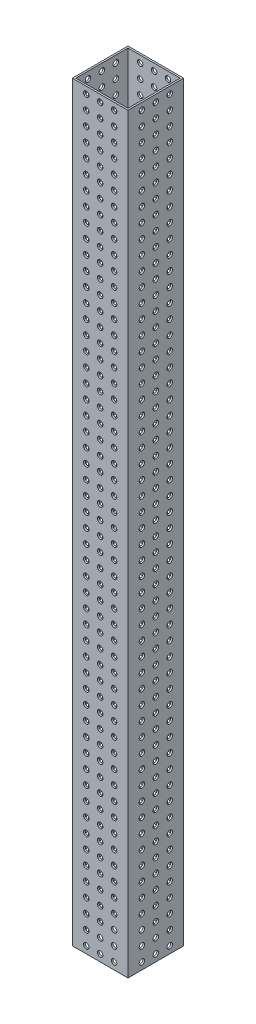
SolidWorks part; units mm, degrees
ref_plane "Front Plane" through (0, 0, 0) normal (0, 0, 1) x (1, 0, 0)
ref_plane "Top Plane" through (0, 0, 0) normal (0, 1, 0) x (1, 0, 0)
ref_plane "Right Plane" through (0, 0, 0) normal (1, 0, 0) x (0, 0, -1)
sketch "Sketch1" plane through (0, 0, 0) normal (0, 1, 0) x (1, 0, 0)
  line L1 (-25.4, 25.4) -> (25.4, 25.4)
  line L2 (-25.4, 25.4) -> (-25.4, -25.4)
  line L3 (-25.4, -25.4) -> (25.4, -25.4)
  line L4 (25.4, 25.4) -> (25.4, -25.4)
  line L5 (-25.4, 25.4) -> (25.4, -25.4) construction
  line L6 (-25.4, -25.4) -> (25.4, 25.4) construction
  line L7 (23.8125, 23.8125) -> (-23.8125, 23.8125)
  line L8 (23.8125, 23.8125) -> (23.8125, -23.8125)
  line L9 (23.8125, -23.8125) -> (-23.8125, -23.8125)
  line L10 (-23.8125, 23.8125) -> (-23.8125, -23.8125)
  line L11 (23.8125, 23.8125) -> (-23.8125, -23.8125) construction
  line L12 (23.8125, -23.8125) -> (-23.8125, 23.8125) construction
  point P0 (0, 0)
  point P6 (0, 0)
  dimension "D1" = 50.8
  dimension "D2" = 50.8
  dimension "D3" = 1.5875
  dimension "D4" = 1.5875
extrude "Boss-Extrude1" add sketch "Sketch1" along normal blind 685.8
sketch "Sketch2" plane through (0, 0, 25.4) normal (0, 0, 1) x (1, 0, 0)
  line L0 (0, 685.8) -> (0, 0) construction
  line L1 (-25.4, 685.8) -> (25.4, 685.8) construction
  line L2 (-25.4, 685.8) -> (-25.4, 0) construction
  line L3 (-6.35, -314.2) -> (-6.35, 49685.8) construction
  circle A0 centre (-12.7, 679.45) radius 2.4892
  circle A1 centre (-12.7, 666.75) radius 2.4892
  circle A2 centre (-12.7, 654.05) radius 2.4892
  circle A3 centre (-12.7, 641.35) radius 2.4892
  circle A4 centre (-12.7, 628.65) radius 2.4892
  circle A5 centre (-12.7, 615.95) radius 2.4892
  circle A6 centre (-12.7, 603.25) radius 2.4892
  circle A7 centre (-12.7, 590.55) radius 2.4892
  circle A8 centre (-12.7, 577.85) radius 2.4892
  circle A9 centre (-12.7, 565.15) radius 2.4892
  circle A10 centre (-12.7, 552.45) radius 2.4892
  circle A11 centre (-12.7, 539.75) radius 2.4892
  circle A12 centre (-12.7, 527.05) radius 2.4892
  circle A13 centre (-12.7, 514.35) radius 2.4892
  circle A14 centre (-12.7, 501.65) radius 2.4892
  circle A15 centre (-12.7, 488.95) radius 2.4892
  circle A16 centre (-12.7, 476.25) radius 2.4892
  circle A17 centre (-12.7, 463.55) radius 2.4892
  circle A18 centre (-12.7, 450.85) radius 2.4892
  circle A19 centre (-12.7, 438.15) radius 2.4892
  circle A20 centre (-12.7, 425.45) radius 2.4892
  circle A21 centre (-12.7, 412.75) radius 2.4892
  circle A22 centre (-12.7, 400.05) radius 2.4892
  circle A23 centre (-12.7, 387.35) radius 2.4892
  circle A24 centre (-12.7, 374.65) radius 2.4892
  circle A25 centre (-12.7, 361.95) radius 2.4892
  circle A26 centre (-12.7, 349.25) radius 2.4892
  circle A27 centre (-12.7, 336.55) radius 2.4892
  circle A28 centre (-12.7, 323.85) radius 2.4892
  circle A29 centre (-12.7, 311.15) radius 2.4892
  circle A30 centre (-12.7, 298.45) radius 2.4892
  circle A31 centre (-12.7, 285.75) radius 2.4892
  circle A32 centre (-12.7, 273.05) radius 2.4892
  circle A33 centre (-12.7, 260.35) radius 2.4892
  circle A34 centre (-12.7, 247.65) radius 2.4892
  circle A35 centre (-12.7, 234.95) radius 2.4892
  circle A36 centre (-12.7, 222.25) radius 2.4892
  circle A37 centre (-12.7, 209.55) radius 2.4892
  circle A38 centre (-12.7, 196.85) radius 2.4892
  circle A39 centre (-12.7, 184.15) radius 2.4892
  circle A40 centre (-12.7, 171.45) radius 2.4892
  circle A41 centre (-12.7, 158.75) radius 2.4892
  circle A42 centre (-12.7, 146.05) radius 2.4892
  circle A43 centre (-12.7, 133.35) radius 2.4892
  circle A44 centre (-12.7, 120.65) radius 2.4892
  circle A45 centre (-12.7, 107.95) radius 2.4892
  circle A46 centre (-12.7, 95.25) radius 2.4892
  circle A47 centre (-12.7, 82.55) radius 2.4892
  circle A48 centre (-12.7, 69.85) radius 2.4892
  circle A49 centre (-12.7, 57.15) radius 2.4892
  circle A50 centre (-12.7, 44.45) radius 2.4892
  circle A51 centre (-12.7, 31.75) radius 2.4892
  circle A52 centre (-12.7, 19.05) radius 2.4892
  circle A53 centre (-12.7, 6.35) radius 2.4892
  circle A54 centre (12.7, 6.35) radius 2.4892
  circle A55 centre (12.7, 19.05) radius 2.4892
  circle A56 centre (12.7, 31.75) radius 2.4892
  circle A57 centre (12.7, 44.45) radius 2.4892
  circle A58 centre (12.7, 57.15) radius 2.4892
  circle A59 centre (12.7, 69.85) radius 2.4892
  circle A60 centre (12.7, 82.55) radius 2.4892
  circle A61 centre (12.7, 95.25) radius 2.4892
  circle A62 centre (12.7, 107.95) radius 2.4892
  circle A63 centre (12.7, 120.65) radius 2.4892
  circle A64 centre (12.7, 133.35) radius 2.4892
  circle A65 centre (12.7, 146.05) radius 2.4892
  circle A66 centre (12.7, 158.75) radius 2.4892
  circle A67 centre (12.7, 171.45) radius 2.4892
  circle A68 centre (12.7, 184.15) radius 2.4892
  circle A69 centre (12.7, 196.85) radius 2.4892
  circle A70 centre (12.7, 209.55) radius 2.4892
  circle A71 centre (12.7, 222.25) radius 2.4892
  circle A72 centre (12.7, 234.95) radius 2.4892
  circle A73 centre (12.7, 247.65) radius 2.4892
  circle A74 centre (12.7, 260.35) radius 2.4892
  circle A75 centre (12.7, 273.05) radius 2.4892
  circle A76 centre (12.7, 285.75) radius 2.4892
  circle A77 centre (12.7, 298.45) radius 2.4892
  circle A78 centre (12.7, 311.15) radius 2.4892
  circle A79 centre (12.7, 323.85) radius 2.4892
  circle A80 centre (12.7, 336.55) radius 2.4892
  circle A81 centre (12.7, 374.65) radius 2.4892
  circle A82 centre (12.7, 361.95) radius 2.4892
  circle A83 centre (12.7, 349.25) radius 2.4892
  circle A84 centre (12.7, 387.35) radius 2.4892
  circle A85 centre (12.7, 400.05) radius 2.4892
  circle A86 centre (12.7, 412.75) radius 2.4892
  circle A87 centre (12.7, 425.45) radius 2.4892
  circle A88 centre (12.7, 438.15) radius 2.4892
  circle A89 centre (12.7, 450.85) radius 2.4892
  circle A90 centre (12.7, 463.55) radius 2.4892
  circle A91 centre (12.7, 476.25) radius 2.4892
  circle A92 centre (12.7, 488.95) radius 2.4892
  circle A93 centre (12.7, 501.65) radius 2.4892
  circle A94 centre (12.7, 514.35) radius 2.4892
  circle A95 centre (12.7, 527.05) radius 2.4892
  circle A96 centre (12.7, 539.75) radius 2.4892
  circle A97 centre (12.7, 552.45) radius 2.4892
  circle A98 centre (12.7, 565.15) radius 2.4892
  circle A99 centre (12.7, 577.85) radius 2.4892
  circle A100 centre (12.7, 590.55) radius 2.4892
  circle A101 centre (12.7, 603.25) radius 2.4892
  circle A102 centre (12.7, 615.95) radius 2.4892
  circle A103 centre (12.7, 628.65) radius 2.4892
  circle A104 centre (12.7, 641.35) radius 2.4892
  circle A105 centre (12.7, 654.05) radius 2.4892
  circle A106 centre (12.7, 666.75) radius 2.4892
  circle A107 centre (12.7, 679.45) radius 2.4892
  circle A108 centre (0, 6.35) radius 2.4892
  circle A109 centre (0, 19.05) radius 2.4892
  circle A110 centre (0, 31.75) radius 2.4892
  circle A111 centre (0, 44.45) radius 2.4892
  circle A112 centre (0, 57.15) radius 2.4892
  circle A113 centre (0, 69.85) radius 2.4892
  circle A114 centre (0, 82.55) radius 2.4892
  circle A115 centre (0, 95.25) radius 2.4892
  circle A116 centre (0, 107.95) radius 2.4892
  circle A117 centre (0, 120.65) radius 2.4892
  circle A118 centre (0, 133.35) radius 2.4892
  circle A119 centre (0, 146.05) radius 2.4892
  circle A120 centre (0, 158.75) radius 2.4892
  circle A121 centre (0, 171.45) radius 2.4892
  circle A122 centre (0, 184.15) radius 2.4892
  circle A123 centre (0, 196.85) radius 2.4892
  circle A124 centre (0, 209.55) radius 2.4892
  circle A125 centre (0, 222.25) radius 2.4892
  circle A126 centre (0, 234.95) radius 2.4892
  circle A127 centre (0, 247.65) radius 2.4892
  circle A128 centre (0, 260.35) radius 2.4892
  circle A129 centre (0, 273.05) radius 2.4892
  circle A130 centre (0, 285.75) radius 2.4892
  circle A131 centre (0, 298.45) radius 2.4892
  circle A132 centre (0, 311.15) radius 2.4892
  circle A133 centre (0, 323.85) radius 2.4892
  circle A134 centre (0, 336.55) radius 2.4892
  circle A135 centre (0, 349.25) radius 2.4892
  circle A136 centre (0, 361.95) radius 2.4892
  circle A137 centre (0, 374.65) radius 2.4892
  circle A138 centre (0, 387.35) radius 2.4892
  circle A139 centre (0, 400.05) radius 2.4892
  circle A140 centre (0, 412.75) radius 2.4892
  circle A141 centre (0, 425.45) radius 2.4892
  circle A142 centre (0, 438.15) radius 2.4892
  circle A143 centre (0, 450.85) radius 2.4892
  circle A144 centre (0, 463.55) radius 2.4892
  circle A145 centre (0, 476.25) radius 2.4892
  circle A146 centre (0, 488.95) radius 2.4892
  circle A147 centre (0, 501.65) radius 2.4892
  circle A148 centre (0, 514.35) radius 2.4892
  circle A149 centre (0, 527.05) radius 2.4892
  circle A150 centre (0, 539.75) radius 2.4892
  circle A151 centre (0, 552.45) radius 2.4892
  circle A152 centre (0, 565.15) radius 2.4892
  circle A153 centre (0, 577.85) radius 2.4892
  circle A154 centre (0, 590.55) radius 2.4892
  circle A155 centre (0, 603.25) radius 2.4892
  circle A156 centre (0, 615.95) radius 2.4892
  circle A157 centre (0, 628.65) radius 2.4892
  circle A158 centre (0, 641.35) radius 2.4892
  circle A159 centre (0, 654.05) radius 2.4892
  circle A160 centre (0, 666.75) radius 2.4892
  circle A161 centre (0, 679.45) radius 2.4892
  dimension "D1" = 4.9784
  dimension "D2" = 6.35
  dimension "D3" = 12.7
  dimension "D5" = 12.7
  dimension "D6" = 6.35
  dimension "D4" = 54
extrude "Cut-Extrude1" cut sketch "Sketch2" against normal through all
sketch "Sketch4" plane through (25.4, 0, 0) normal (1, 0, 0) x (0, 0, -1)
  line L0 (0, 685.8) -> (0, 0) construction
  line L1 (-25.4, 685.8) -> (25.4, 685.8) construction
  line L2 (-25.4, 685.8) -> (-25.4, 0) construction
  line L3 (-6.35, -314.2) -> (-6.35, 49685.8) construction
  circle A0 centre (-12.7, 679.45) radius 2.4892
  circle A1 centre (-12.7, 666.75) radius 2.4892
  circle A2 centre (-12.7, 654.05) radius 2.4892
  circle A3 centre (-12.7, 641.35) radius 2.4892
  circle A4 centre (-12.7, 628.65) radius 2.4892
  circle A5 centre (-12.7, 615.95) radius 2.4892
  circle A6 centre (-12.7, 603.25) radius 2.4892
  circle A7 centre (-12.7, 590.55) radius 2.4892
  circle A8 centre (-12.7, 577.85) radius 2.4892
  circle A9 centre (-12.7, 565.15) radius 2.4892
  circle A10 centre (-12.7, 552.45) radius 2.4892
  circle A11 centre (-12.7, 539.75) radius 2.4892
  circle A12 centre (-12.7, 527.05) radius 2.4892
  circle A13 centre (-12.7, 514.35) radius 2.4892
  circle A14 centre (-12.7, 501.65) radius 2.4892
  circle A15 centre (-12.7, 488.95) radius 2.4892
  circle A16 centre (-12.7, 476.25) radius 2.4892
  circle A17 centre (-12.7, 463.55) radius 2.4892
  circle A18 centre (-12.7, 450.85) radius 2.4892
  circle A19 centre (-12.7, 438.15) radius 2.4892
  circle A20 centre (-12.7, 425.45) radius 2.4892
  circle A21 centre (-12.7, 412.75) radius 2.4892
  circle A22 centre (-12.7, 400.05) radius 2.4892
  circle A23 centre (-12.7, 387.35) radius 2.4892
  circle A24 centre (-12.7, 374.65) radius 2.4892
  circle A25 centre (-12.7, 361.95) radius 2.4892
  circle A26 centre (-12.7, 349.25) radius 2.4892
  circle A27 centre (-12.7, 336.55) radius 2.4892
  circle A28 centre (-12.7, 323.85) radius 2.4892
  circle A29 centre (-12.7, 311.15) radius 2.4892
  circle A30 centre (-12.7, 298.45) radius 2.4892
  circle A31 centre (-12.7, 285.75) radius 2.4892
  circle A32 centre (-12.7, 273.05) radius 2.4892
  circle A33 centre (-12.7, 260.35) radius 2.4892
  circle A34 centre (-12.7, 247.65) radius 2.4892
  circle A35 centre (-12.7, 234.95) radius 2.4892
  circle A36 centre (-12.7, 222.25) radius 2.4892
  circle A37 centre (-12.7, 209.55) radius 2.4892
  circle A38 centre (-12.7, 196.85) radius 2.4892
  circle A39 centre (-12.7, 184.15) radius 2.4892
  circle A40 centre (-12.7, 171.45) radius 2.4892
  circle A41 centre (-12.7, 158.75) radius 2.4892
  circle A42 centre (-12.7, 146.05) radius 2.4892
  circle A43 centre (-12.7, 133.35) radius 2.4892
  circle A44 centre (-12.7, 120.65) radius 2.4892
  circle A45 centre (-12.7, 107.95) radius 2.4892
  circle A46 centre (-12.7, 95.25) radius 2.4892
  circle A47 centre (-12.7, 82.55) radius 2.4892
  circle A48 centre (-12.7, 69.85) radius 2.4892
  circle A49 centre (-12.7, 57.15) radius 2.4892
  circle A50 centre (-12.7, 44.45) radius 2.4892
  circle A51 centre (-12.7, 31.75) radius 2.4892
  circle A52 centre (-12.7, 19.05) radius 2.4892
  circle A53 centre (-12.7, 6.35) radius 2.4892
  circle A54 centre (12.7, 273.05) radius 2.4892
  circle A55 centre (12.7, 285.75) radius 2.4892
  circle A56 centre (12.7, 298.45) radius 2.4892
  circle A57 centre (12.7, 311.15) radius 2.4892
  circle A58 centre (12.7, 323.85) radius 2.4892
  circle A59 centre (12.7, 336.55) radius 2.4892
  circle A60 centre (12.7, 349.25) radius 2.4892
  circle A61 centre (12.7, 361.95) radius 2.4892
  circle A62 centre (12.7, 374.65) radius 2.4892
  circle A63 centre (12.7, 387.35) radius 2.4892
  circle A64 centre (12.7, 400.05) radius 2.4892
  circle A65 centre (12.7, 412.75) radius 2.4892
  circle A66 centre (12.7, 425.45) radius 2.4892
  circle A67 centre (12.7, 438.15) radius 2.4892
  circle A68 centre (12.7, 450.85) radius 2.4892
  circle A69 centre (12.7, 463.55) radius 2.4892
  circle A70 centre (12.7, 476.25) radius 2.4892
  circle A71 centre (12.7, 488.95) radius 2.4892
  circle A72 centre (12.7, 501.65) radius 2.4892
  circle A73 centre (12.7, 514.35) radius 2.4892
  circle A74 centre (12.7, 527.05) radius 2.4892
  circle A75 centre (12.7, 539.75) radius 2.4892
  circle A76 centre (12.7, 552.45) radius 2.4892
  circle A77 centre (12.7, 565.15) radius 2.4892
  circle A78 centre (12.7, 577.85) radius 2.4892
  circle A79 centre (12.7, 590.55) radius 2.4892
  circle A80 centre (12.7, 603.25) radius 2.4892
  circle A81 centre (12.7, 615.95) radius 2.4892
  circle A82 centre (12.7, 628.65) radius 2.4892
  circle A83 centre (12.7, 641.35) radius 2.4892
  circle A84 centre (12.7, 654.05) radius 2.4892
  circle A85 centre (12.7, 666.75) radius 2.4892
  circle A86 centre (12.7, 19.05) radius 2.4892
  circle A87 centre (12.7, 31.75) radius 2.4892
  circle A88 centre (12.7, 44.45) radius 2.4892
  circle A89 centre (12.7, 57.15) radius 2.4892
  circle A90 centre (12.7, 69.85) radius 2.4892
  circle A91 centre (12.7, 82.55) radius 2.4892
  circle A92 centre (12.7, 95.25) radius 2.4892
  circle A93 centre (12.7, 107.95) radius 2.4892
  circle A94 centre (12.7, 120.65) radius 2.4892
  circle A95 centre (12.7, 133.35) radius 2.4892
  circle A96 centre (12.7, 146.05) radius 2.4892
  circle A97 centre (12.7, 158.75) radius 2.4892
  circle A98 centre (12.7, 171.45) radius 2.4892
  circle A99 centre (12.7, 184.15) radius 2.4892
  circle A100 centre (12.7, 196.85) radius 2.4892
  circle A101 centre (12.7, 209.55) radius 2.4892
  circle A102 centre (12.7, 222.25) radius 2.4892
  circle A103 centre (12.7, 234.95) radius 2.4892
  circle A104 centre (12.7, 247.65) radius 2.4892
  circle A105 centre (12.7, 260.35) radius 2.4892
  circle A106 centre (12.7, 6.35) radius 2.4892
  circle A107 centre (12.7, 679.45) radius 2.4892
  circle A108 centre (0, 82.55) radius 2.4892
  circle A109 centre (0, 19.05) radius 2.4892
  circle A110 centre (0, 31.75) radius 2.4892
  circle A111 centre (0, 44.45) radius 2.4892
  circle A112 centre (0, 57.15) radius 2.4892
  circle A113 centre (0, 69.85) radius 2.4892
  circle A114 centre (0, 95.25) radius 2.4892
  circle A115 centre (0, 107.95) radius 2.4892
  circle A116 centre (0, 120.65) radius 2.4892
  circle A117 centre (0, 133.35) radius 2.4892
  circle A118 centre (0, 146.05) radius 2.4892
  circle A119 centre (0, 158.75) radius 2.4892
  circle A120 centre (0, 171.45) radius 2.4892
  circle A121 centre (0, 184.15) radius 2.4892
  circle A122 centre (0, 196.85) radius 2.4892
  circle A123 centre (0, 209.55) radius 2.4892
  circle A124 centre (0, 222.25) radius 2.4892
  circle A125 centre (0, 234.95) radius 2.4892
  circle A126 centre (0, 247.65) radius 2.4892
  circle A127 centre (0, 260.35) radius 2.4892
  circle A128 centre (0, 273.05) radius 2.4892
  circle A129 centre (0, 285.75) radius 2.4892
  circle A130 centre (0, 298.45) radius 2.4892
  circle A131 centre (0, 311.15) radius 2.4892
  circle A132 centre (0, 323.85) radius 2.4892
  circle A133 centre (0, 336.55) radius 2.4892
  circle A134 centre (0, 361.95) radius 2.4892
  circle A135 centre (0, 374.65) radius 2.4892
  circle A136 centre (0, 387.35) radius 2.4892
  circle A137 centre (0, 400.05) radius 2.4892
  circle A138 centre (0, 412.75) radius 2.4892
  circle A139 centre (0, 425.45) radius 2.4892
  circle A140 centre (0, 438.15) radius 2.4892
  circle A141 centre (0, 450.85) radius 2.4892
  circle A142 centre (0, 463.55) radius 2.4892
  circle A143 centre (0, 476.25) radius 2.4892
  circle A144 centre (0, 488.95) radius 2.4892
  circle A145 centre (0, 501.65) radius 2.4892
  circle A146 centre (0, 514.35) radius 2.4892
  circle A147 centre (0, 527.05) radius 2.4892
  circle A148 centre (0, 539.75) radius 2.4892
  circle A149 centre (0, 552.45) radius 2.4892
  circle A150 centre (0, 565.15) radius 2.4892
  circle A151 centre (0, 577.85) radius 2.4892
  circle A152 centre (0, 590.55) radius 2.4892
  circle A153 centre (0, 603.25) radius 2.4892
  circle A154 centre (0, 615.95) radius 2.4892
  circle A155 centre (0, 628.65) radius 2.4892
  circle A156 centre (0, 641.35) radius 2.4892
  circle A157 centre (0, 654.05) radius 2.4892
  circle A158 centre (0, 666.75) radius 2.4892
  circle A159 centre (0, 679.45) radius 2.4892
  circle A160 centre (0, 349.25) radius 2.4892
  circle A161 centre (0, 6.35) radius 2.4892
  dimension "D1" = 4.9784
  dimension "D2" = 12.7
  dimension "D7" = 12.7
  dimension "D3" = 6.35
  dimension "D5" = 12.7
  dimension "D6" = 6.35
  dimension "D4" = 54
extrude "Cut-Extrude2" cut sketch "Sketch4" against normal through all
